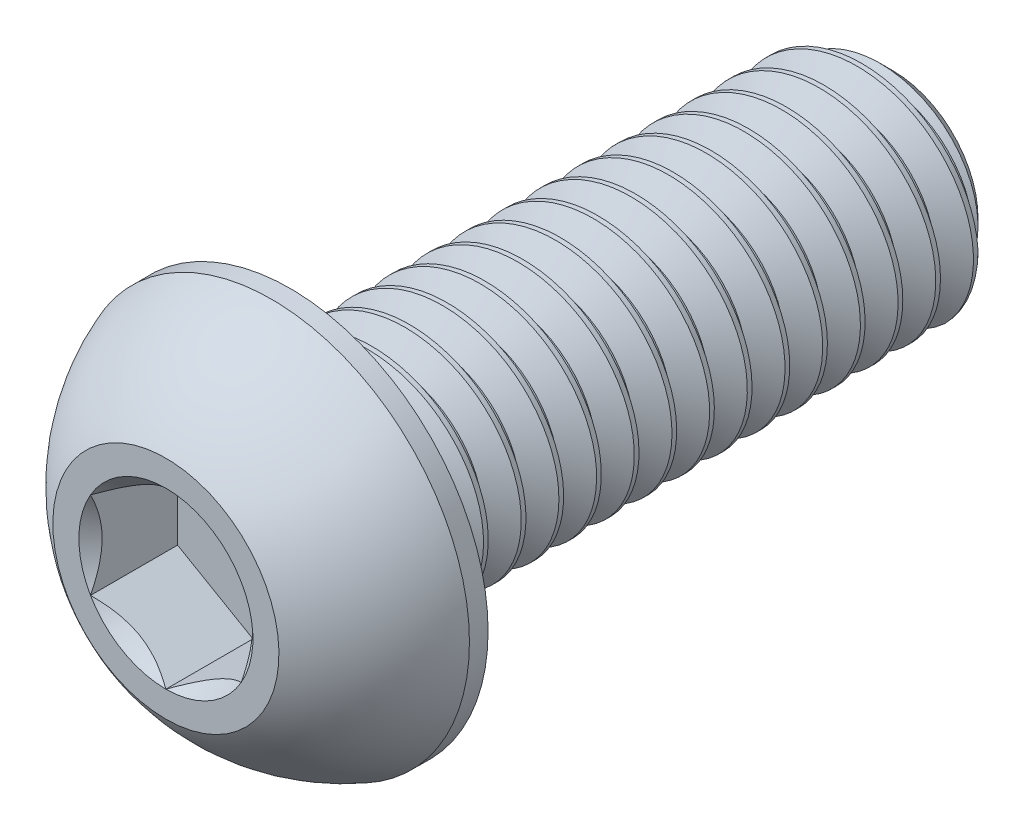
SolidWorks part; units mm, degrees
ref_plane "Front" through (0, 0, 0) normal (0, 0, 1) x (1, 0, 0)
ref_plane "Top" through (0, 0, 0) normal (0, 1, 0) x (1, 0, 0)
ref_plane "Right" through (0, 0, 0) normal (1, 0, 0) x (0, 0, -1)
sketch "Sketch1" plane through (0, 0, 0) normal (1, 0, 0) x (0, 0, -1)
  line L2 (3.3, 3) -> (19.3, 3)
  line L3 (19.3, 3) -> (19.3, 0)
  line L4 (19.3, 0) -> (3.3, 0)
  line L6 (2.805, 5.25) -> (3.3, 5.25) construction
  line L7 (19.3, 3) -> (19.3, -3) construction
  line L8 (0, 0) -> (3.3, 0) construction
  line L9 (3.3, 5.25) -> (3.3, -5.25) construction
  line L11 (3.3, 3) -> (3.3, 0)
  line L13 (0, 2) -> (0, -2) construction
  line L14 (0, 2) -> (0, 3) construction
  arc A3 (0, 3) -> (2.805, 5.25) centre (4.7113, 0) cw construction
  dimension "D1" = 0.495
revolve "Revolve1" add sketch "Sketch1" angle 360 mid plane about L4
sketch "Sketch3" plane through (0, 0, -19.3) normal (0, 0, -1) x (-1, 0, 0)
  circle A0 centre (0, 0) radius 3
curve "Helix/Spiral1" pitch 1 height 17 turns 17
sketch "Sketch2" plane through (0, 0, 0) normal (1, 0, 0) x (0, 0, -1)
  line L0 (19.3, 3) -> (20.175, 3)
  line L1 (20.175, 3) -> (19.8, 2.3505)
  line L2 (19.8, 2.3505) -> (19.675, 2.3505)
  line L3 (19.675, 2.3505) -> (19.3, 3)
  line L4 (19.4875, 2.6752) -> (19.9875, 2.6752) construction
  dimension "D1" = 60
  dimension "D2" = 0.125
  dimension "D3" = 0.5
chamfer "Chamfer1" distance 0.75 angle 45 1 edges at (0, 3, -19.3)
sweep "Cut-Sweep1" cut profiles "Sketch2" path "Helix/Spiral1"
sketch "Sketch7" plane through (0, 0, 0) normal (1, 0, 0) x (0, 0, -1)
  line L6 (2.805, 5.25) -> (3.3, 5.25) construction
  line L8 (0, 0) -> (3.3, 0) construction
  line L11 (3.3, 5.25) -> (3.3, -5.25) construction
  line L12 (2.805, 5.25) -> (3.3, 5.25)
  line L13 (0, 0) -> (3.3, 0)
  line L14 (0, 2) -> (0, -2) construction
  line L15 (3.3, 5.25) -> (3.3, 0)
  line L16 (0, 3) -> (0, 0)
  arc A2 (2.805, 5.25) -> (0, 3) centre (4.7113, 0) ccw construction
  arc A3 (2.805, 5.25) -> (0, 3) centre (4.7113, 0) ccw
revolve "Revolve2" add sketch "Sketch7" angle 360 mid plane about L13
sketch "Sketch5" plane through (0, 0, 0) normal (0, 0, 1) x (1, 0, 0)
  line L1 (2, -1.1547) -> (2, 1.1547)
  line L2 (2, 1.1547) -> (0, 2.3094)
  line L3 (0, 2.3094) -> (-2, 1.1547)
  line L4 (-2, 1.1547) -> (-2, -1.1547)
  line L5 (-2, -1.1547) -> (0, -2.3094)
  line L6 (0, -2.3094) -> (2, -1.1547)
  circle A0 centre (0, 0) radius 2 construction
extrude "Cut-Extrude2" cut sketch "Sketch5" against normal blind 2.31
sketch "Sketch6" plane through (0, 0, 0) normal (0, 0, 1) x (1, 0, 0)
  circle A0 centre (0, 0) radius 2.3094
extrude "Cut-Extrude3" cut sketch "Sketch6" against normal blind 2.31 draft 45
sketch "Sketch9" [suppressed] plane through (0, 0, -3.3) normal (0, 0, 1) x (1, 0, 0)
  circle A2 centre (0, 0) radius 3
extrude "Boss-Extrude2" [suppressed] add sketch "Sketch9" against normal offset from surface (11 mm away) 22
sketch "Sketch10" plane through (0, 0, 0) normal (1, 0, 0) x (0, 0, -1)
  line L0 (19.3, 3) -> (19.3, -3) construction
  point P0 (17.8, -3)
  dimension "D1" = 1.5
equation "\"D3@Helix/Spiral1\" = \"Lg@Sketch1\" + \"D4@Helix/Spiral1\""
equation "\"D2@Sketch2\" = \"D4@Helix/Spiral1\" * .125"
equation "\"D3@Sketch2\" = \"D4@Helix/Spiral1\" * .5"
equation "\"D1@Chamfer1\" = \"D4@Helix/Spiral1\" * .75"
equation "\"D1@Cut-Extrude2\" = \"Head Ht@Sketch1\" * .7"
equation "\"D1@Sketch1\" = \"Head Ht@Sketch1\" * .15"
equation "\"D1@Sketch10\" = \"D4@Helix/Spiral1\" * 1.5"
equation "\"D1@Cut-Extrude3\" = \"D1@Cut-Extrude2\""
